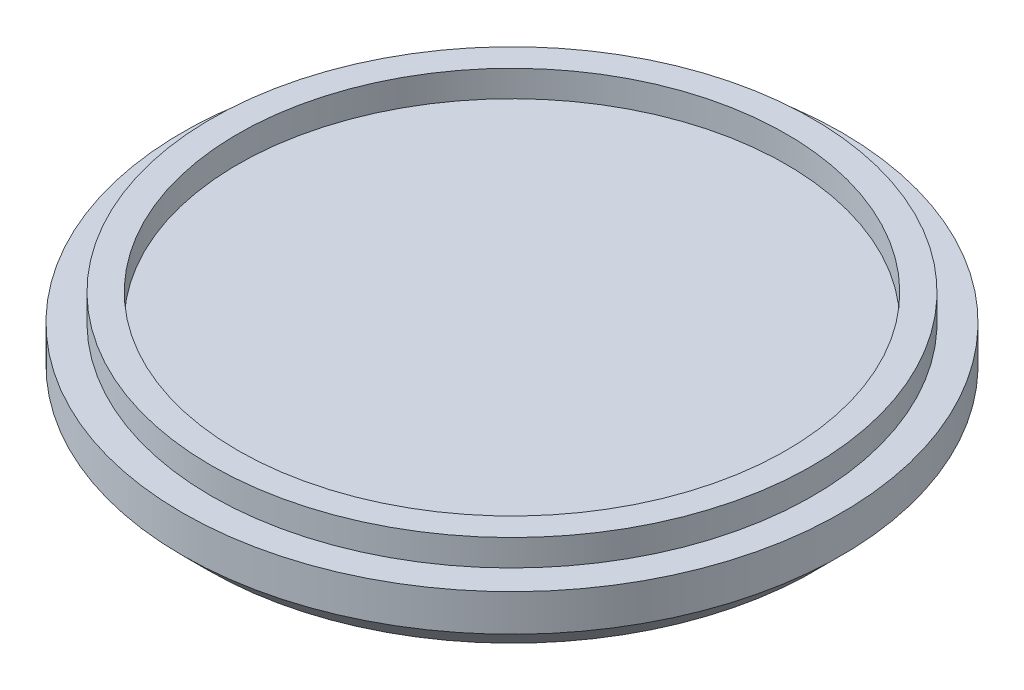
SolidWorks part; units mm, degrees
ref_plane "Front Plane" through (0, 0, 0) normal (0, 0, 1) x (1, 0, 0)
ref_plane "Top Plane" through (0, 0, 0) normal (0, 1, 0) x (1, 0, 0)
ref_plane "Right Plane" through (0, 0, 0) normal (1, 0, 0) x (0, 0, -1)
sketch "Sketch1" plane through (0, 0, 0) normal (0, 1, 0) x (1, 0, 0)
  circle A0 centre (0, 0) radius 12.5
  dimension "D1" = 25
extrude "Boss-Extrude1" add sketch "Sketch1" along normal blind 1.4 and the other way blind 1
sketch "Sketch2" plane through (0, 1.4, 0) normal (0, 1, 0) x (1, 0, 0)
  circle A0 centre (0, 0) radius 11.4
  circle A1 centre (0, 0) radius 10.4
  dimension "D1" = 22.8
  dimension "D2" = 1
extrude "Boss-Extrude2" add sketch "Sketch2" along normal blind 1
chamfer "Chamfer1" distance 1 angle 45 1 edges at (0, -1, 12.5)
sketch "Sketch3" plane through (0, -1, 0) normal (0, -1, 0) x (1, 0, 0)
  line L0 (0, 0) -> (0, -7) construction
  line L1 (9.1241, -7) -> (-9.1241, -7) construction
  circle A0 centre (0, 0) radius 11.5 construction
  point P5 (0, -7)
  dimension "D1" = 7
sketch "Sketch4" [suppressed] plane through (0, -1, 0) normal (0, -1, 0) x (1, 0, 0)
  text T0 "S" font "Arial Rounded MT Bold" height 14
extrude "Cut-Extrude2" [suppressed] cut sketch "Sketch4" against normal blind 0.4
sketch "Sketch5" [suppressed] plane through (0, -1, 0) normal (0, -1, 0) x (1, 0, 0)
  text T0 "T" font "Arial Rounded MT Bold" height 14
extrude "Cut-Extrude3" [suppressed] cut sketch "Sketch5" against normal blind 0.4
sketch "Sketch6" [suppressed] plane through (0, -1, 0) normal (0, -1, 0) x (1, 0, 0)
  text T0 "A" font "Arial Rounded MT Bold" height 14
extrude "Cut-Extrude4" [suppressed] cut sketch "Sketch6" against normal blind 0.4
sketch "Sketch7" [suppressed] plane through (0, -1, 0) normal (0, -1, 0) x (1, 0, 0)
  text T0 "L" font "Arial Rounded MT Bold" height 14
extrude "Cut-Extrude5" [suppressed] cut sketch "Sketch7" against normal blind 0.4
sketch "Sketch8" plane through (0, -1, 0) normal (0, -1, 0) x (1, 0, 0)
  text T0 "E" font "Arial Rounded MT Bold" height 14
extrude "Cut-Extrude6" cut sketch "Sketch8" against normal blind 0.4
